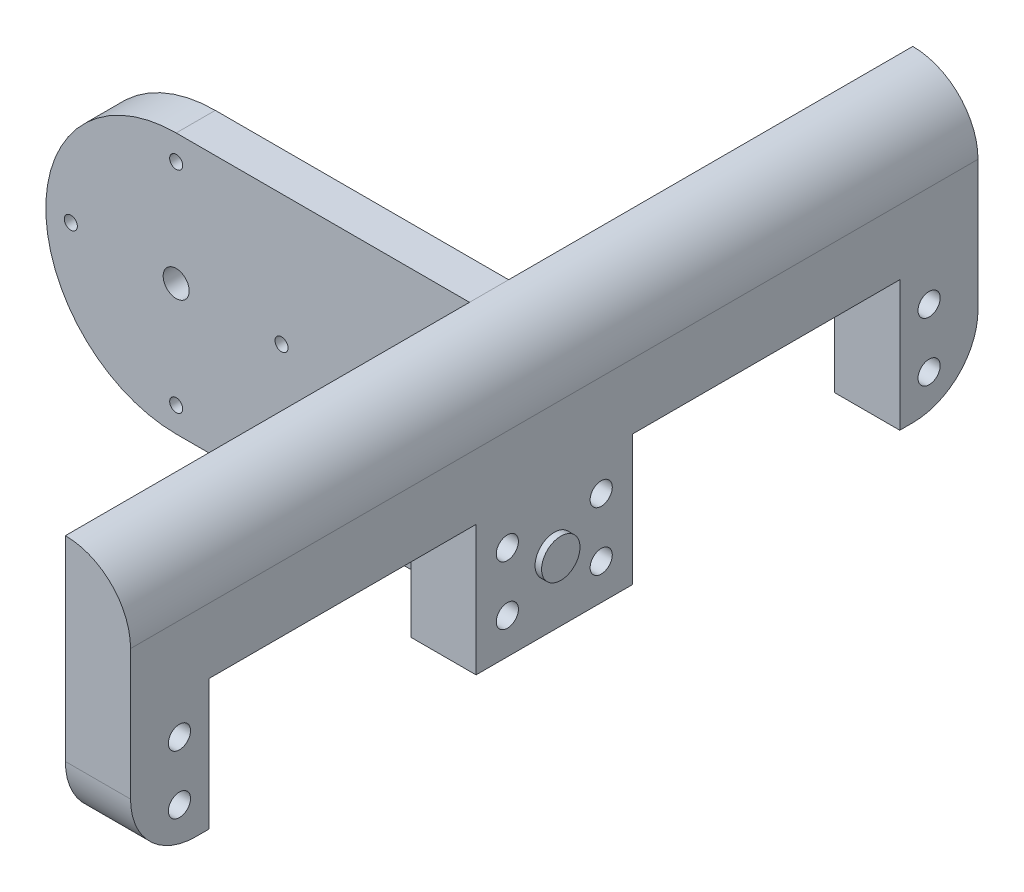
SolidWorks part; units mm, degrees
ref_plane "Front" through (0, 0, 0) normal (0, 0, 1) x (1, 0, 0)
ref_plane "Top" through (0, 0, 0) normal (0, 1, 0) x (1, 0, 0)
ref_plane "Right" through (0, 0, 0) normal (1, 0, 0) x (0, 0, -1)
sketch "스케치1" plane through (0, 0, 0) normal (0, 0, 1) x (1, 0, 0)
  line L0 (0, 20) -> (45, 20)
  line L2 (45, 20) -> (45, -20)
  line L3 (0, -20) -> (45, -20)
  circle A0 centre (0, 0) radius 2
  circle A2 centre (0, 16.16) radius 1
  arc A18 (0, 20) -> (0, -20) centre (0, 0) ccw
  circle A19 centre (16.16, 0) radius 1
  circle A20 centre (0, -16.16) radius 1
  circle A21 centre (-16.16, 0) radius 1
  point P18 (0, 0)
  dimension "D1" = 45
extrude "보스-돌출1" add sketch "스케치1" along normal blind 3 and the other way blind 3
sketch "스케치2" plane through (45, 0, 0) normal (1, 0, 0) x (0, 0, -1)
  line L0 (0, 20) -> (0, -20) construction
  line L1 (65, 20) -> (-65, 20)
  line L2 (65, 20) -> (65, -20)
  line L3 (65, -20) -> (-65, -20)
  line L4 (-65, 20) -> (-65, -20)
  dimension "D1" = 130
  dimension "D2" = 40
extrude "보스-돌출2" add sketch "스케치2" along normal blind 10
sketch "스케치3" plane through (55, 0, 0) normal (1, 0, 0) x (0, 0, -1)
  line L0 (0, 20) -> (0, -20) construction
  line L1 (65, 20) -> (-65, 20) construction
  line L2 (-65, -20) -> (65, -20) construction
  line L3 (-65, 0) -> (65, 0) construction
  line L4 (-65, 20) -> (-65, -20) construction
  line L5 (65, -20) -> (65, 20) construction
  line L6 (53, -20) -> (12, -20)
  line L7 (-53, -20) -> (-12, -20)
  line L8 (-53, -20) -> (-53, 0)
  line L9 (-53, 0) -> (-12, 0)
  line L10 (-12, -20) -> (-12, 0)
  line L11 (53, -20) -> (53, 0)
  line L12 (53, 0) -> (12, 0)
  line L13 (12, -20) -> (12, 0)
  dimension "D1" = 12
  dimension "D2" = 12
  dimension "D3" = 20
extrude "컷-돌출1" cut sketch "스케치3" against normal blind 10
fillet "필렛1" radius 10 1 edges at (55, 20, 0)
hole_wizard "M3 여유 구멍1" positions "스케치4" profile "스케치5" hole size "M3" standard "KS" end condition up to next
sketch "스케치4" plane through (55, 0, 0) normal (1, 0, 0) x (0, 0, -1)
  point P0 (-57.5, -5.5)
  point P3 (-57.5, -14.5)
  point P6 (-7.2, -5.5)
  point P13 (-7.2, -14.5)
  point P16 (7.2, -5.5)
  point P19 (7.2, -14.5)
  point P22 (57.5, -5.5)
  point P25 (57.5, -14.5)
sketch "스케치5" plane through (55, -5.5, 57.5) normal (0, 1, 0) x (0, 0, -1)
  line L0 (0, 0) -> (0, 10)
  line L1 (0, 10) -> (1.7, 10)
  line L2 (1.7, 10) -> (1.7, 0)
  line L5 (1.7, 0) -> (0, 0)
  line L11 (0, -6.35) -> (0, 107.95) construction
  dimension "관통 구멍 지름" = 3.4
  dimension "관통 구멍 깊이" = 10
fillet "필렛4" radius 10 2 edges at (50, -20, -65) (50, -20, 65)
sketch "스케치6" plane through (55, 0, 0) normal (1, 0, 0) x (0, 0, -1)
  line L0 (-42.5, -10) -> (42.5, -10) construction
  line L1 (0, 0) -> (0, -20) construction
  line L2 (-12, -20) -> (12, -20) construction
  circle A0 centre (0, -10) radius 2.9444
extrude "보스-돌출3" add sketch "스케치6" along normal blind 1
